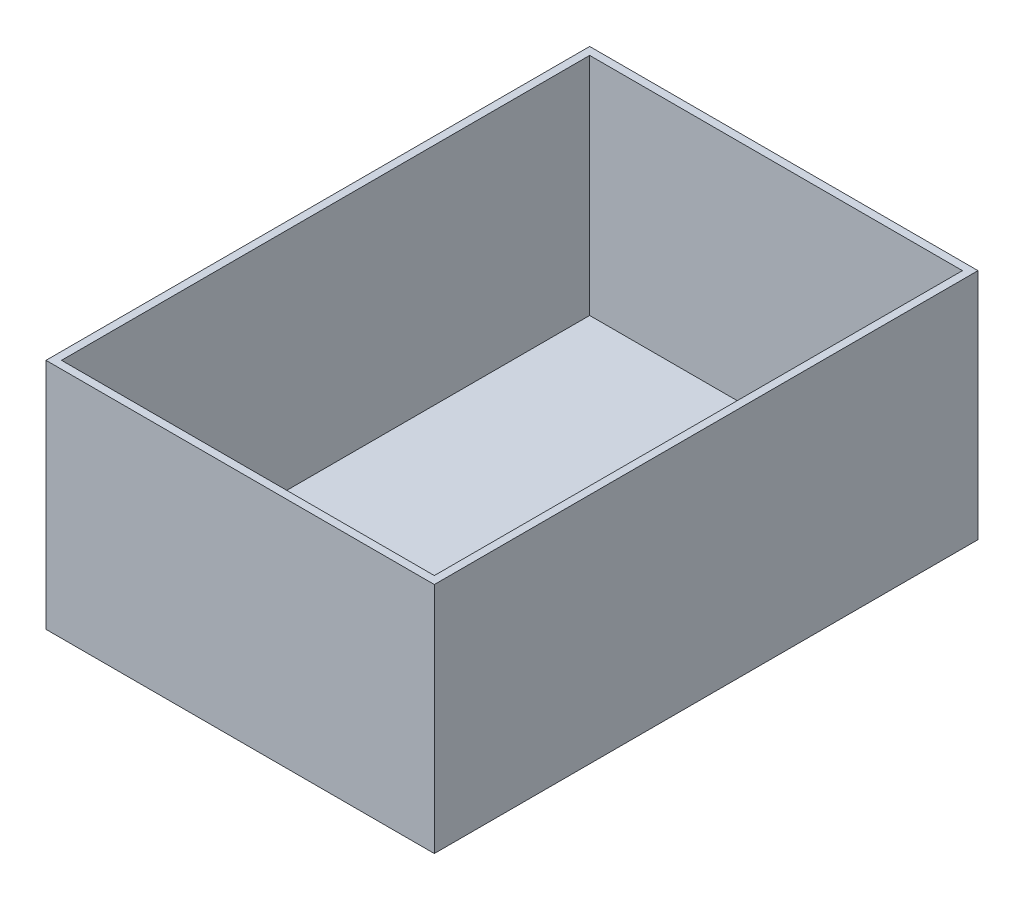
SolidWorks part; units mm, degrees
material "ABS"
ref_plane "Front Plane" through (0, 0, 0) normal (0, 0, 1) x (1, 0, 0)
ref_plane "Top Plane" through (0, 0, 0) normal (0, 1, 0) x (1, 0, 0)
ref_plane "Right Plane" through (0, 0, 0) normal (1, 0, 0) x (0, 0, -1)
ref_axis "X" through (-88.99, 0, 0) along (1, 0, 0)
ref_axis "Y" through (0, 55, 0) along (0, -1, 0)
ref_axis "Z" through (0, 0, -88.99) along (0, 0, 1)
sketch "Sketch4" plane through (0, 0, 0) normal (0, 1, 0) x (1, 0, 0)
  line L1 (0, 0) -> (-250, 0)
  line L2 (0, 0) -> (0, 350)
  line L3 (0, 350) -> (-250, 350)
  line L4 (-250, 0) -> (-250, 350)
  dimension "D1" = 250
  dimension "D2" = 350
extrude "Boss-Extrude2" add sketch "Sketch4" along normal blind 150
shell "Shell1" thickness 5 removed face at (-125, 150, -175)
